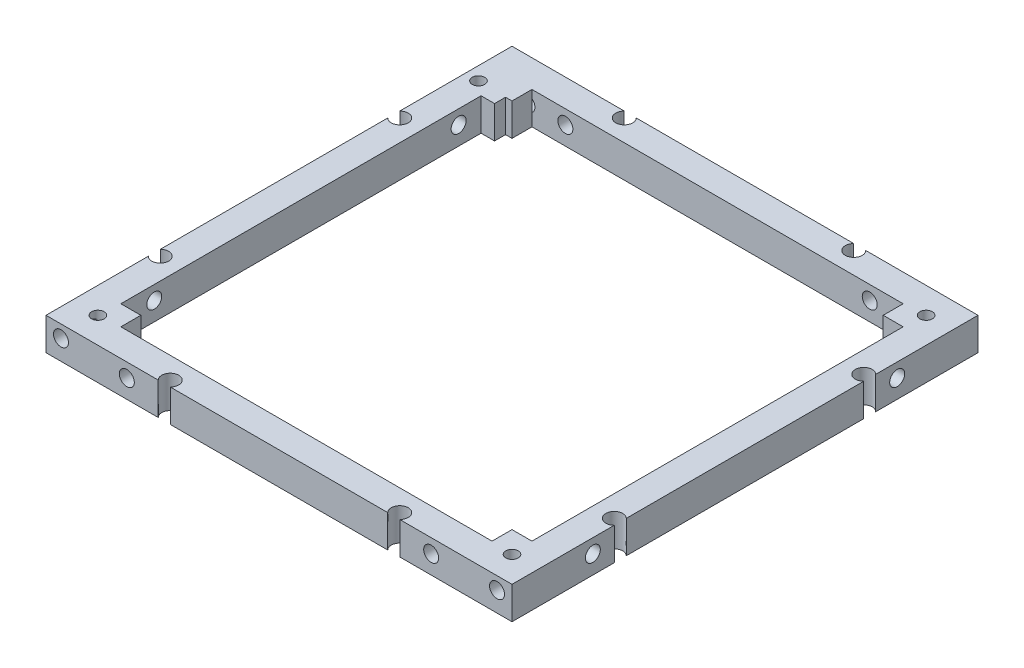
SolidWorks part; units mm, degrees
material "Aluminum"
ref_plane "Front Plane" through (0, 0, 0) normal (0, 0, 1) x (1, 0, 0)
ref_plane "Top Plane" through (0, 0, 0) normal (0, 1, 0) x (1, 0, 0)
ref_plane "Right Plane" through (0, 0, 0) normal (1, 0, 0) x (0, 0, -1)
sketch "Sketch1" plane through (0, 0, 0) normal (0, 1, 0) x (1, 0, 0)
  line L1 (46.7, -46.7) -> (-46.7, -46.7)
  line L2 (46.7, -46.7) -> (46.7, 46.7)
  line L3 (46.7, 46.7) -> (-46.7, 46.7)
  line L4 (-46.7, -46.7) -> (-46.7, 46.7)
  line L5 (46.7, -46.7) -> (-46.7, 46.7) construction
  line L6 (46.7, 46.7) -> (-46.7, -46.7) construction
  line L7 (38.7, -38.7) -> (-38.7, -38.7)
  line L8 (38.7, -38.7) -> (38.7, 38.7)
  line L9 (38.7, 38.7) -> (-38.7, 38.7)
  line L10 (-38.7, -38.7) -> (-38.7, 38.7)
  line L11 (38.7, -38.7) -> (-38.7, 38.7) construction
  line L12 (38.7, 38.7) -> (-38.7, -38.7) construction
  point P0 (0, 0)
  point P6 (0, 0)
  dimension "D1" = 93.4
  dimension "D2" = 93.4
  dimension "D3" = 8
extrude "Boss-Extrude1" add sketch "Sketch1" along normal blind 8
hole_wizard "Ø3.0 (3) Diameter Hole6" positions "Sketch8" profile "Sketch7" hole size "Ø3.0" standard "ANSI Metric"
sketch "Sketch8" plane through (0, 0, 46.7) normal (0, 0, 1) x (1, 0, 0)
  line L0 (46.7, 8) -> (46.7, 0) construction
  line L1 (-46.7, 8) -> (-46.7, 0) construction
  line L2 (-46.7, 0) -> (46.7, 0) construction
  point P0 (43.7, 4)
  point P2 (-43.7, 4)
  dimension "D1" = 3
  dimension "D2" = 3
  dimension "D3" = 4
  dimension "D4" = 4
sketch "Sketch7" plane through (43.7, 4, 46.7) normal (1, 0, 0) x (0, -1, 0)
  line L0 (0, 0) -> (0, 7.5)
  line L1 (0, 7.5) -> (1.5, 7.5)
  line L2 (1.5, 7.5) -> (1.5, 0)
  line L5 (1.5, 0) -> (0, 0)
  line L10 (0, 7.5) -> (-1.5, 7.5) construction
  line L11 (0, -6.35) -> (0, 107.95) construction
  dimension "Hole Dia." = 3
  dimension "Hole Depth" = 7.5
  dimension "Drill Angle" = 180
hole_wizard "Ø3.0 (3) Diameter Hole3" positions "Sketch10" profile "Sketch9" hole size "Ø3.0" standard "ANSI Metric"
sketch "Sketch10" plane through (0, 0, -46.7) normal (0, 0, -1) x (-1, 0, 0)
  line L0 (-46.7, 8) -> (-46.7, 0) construction
  line L1 (46.7, 8) -> (46.7, 0) construction
  line L2 (-46.7, 0) -> (46.7, 0) construction
  point P0 (-43.7, 4)
  point P2 (43.7, 4)
  dimension "D1" = 3
  dimension "D2" = 3
  dimension "D3" = 4
  dimension "D4" = 4
sketch "Sketch9" plane through (43.7, 4, -46.7) normal (1, 0, 0) x (0, 1, 0)
  line L0 (0, 0) -> (0, 7.5)
  line L1 (0, 7.5) -> (1.5, 7.5)
  line L2 (1.5, 7.5) -> (1.5, 0)
  line L5 (1.5, 0) -> (0, 0)
  line L10 (0, 7.5) -> (-1.5, 7.5) construction
  line L11 (0, -6.35) -> (0, 107.95) construction
  dimension "Hole Dia." = 3
  dimension "Hole Depth" = 7.5
  dimension "Drill Angle" = 180
sketch "Sketch27" plane through (0, 8, 0) normal (0, 1, 0) x (1, 0, 0)
  line L0 (-38.7, 38.7) -> (-38.7, -38.7) construction
  line L1 (39.7, -39.7) -> (-39.7, -39.7)
  line L2 (39.7, -39.7) -> (39.7, 39.7)
  line L3 (39.7, 39.7) -> (-39.7, 39.7)
  line L4 (-39.7, -39.7) -> (-39.7, 39.7)
  line L5 (39.7, -39.7) -> (-39.7, 39.7) construction
  line L6 (39.7, 39.7) -> (-39.7, -39.7) construction
  line L7 (38.7, 38.7) -> (-38.7, 38.7) construction
  point P0 (0, 0)
  dimension "D1" = 1
  dimension "D2" = 1
extrude "Cut-Extrude2" cut sketch "Sketch27" against normal blind 10
hole_wizard "Ø3.4 (3.4) Diameter Hole1" positions "Sketch37" profile "Sketch36" hole size "Ø3.4" standard "ANSI Metric" end condition through all
sketch "Sketch37" plane through (0, 0, 0) normal (0, -1, 0) x (-1, 0, 0)
  point P0 (-23, 45.5)
  point P2 (23, 45.5)
  point P4 (45.5, 23)
  point P6 (45.5, -25)
  point P8 (23, -45.5)
  point P10 (-23, -45.5)
  point P12 (-45.5, -25)
  point P14 (-45.5, 25)
sketch "Sketch36" plane through (23, 0, -45.5) normal (1, 0, 0) x (0, 0, -1)
  line L0 (0, 0) -> (0, 8)
  line L1 (0, 8) -> (1.7, 8)
  line L2 (1.7, 8) -> (1.7, 0)
  line L5 (1.7, 0) -> (0, 0)
  line L11 (0, -6.35) -> (0, 107.95) construction
  dimension "Thru Hole Dia." = 3.4
  dimension "Thru Hole Depth" = 8
sketch "Sketch38" plane through (0, 8, 0) normal (0, 1, 0) x (1, 0, 0)
  line L0 (46.7, 46.7) -> (24.2042, 46.7) construction
  line L1 (41.2, -41.2) -> (-41.2, -41.2)
  line L2 (41.2, -41.2) -> (41.2, 41.2)
  line L3 (41.2, 41.2) -> (-41.2, 41.2)
  line L4 (-41.2, -41.2) -> (-41.2, 41.2)
  line L5 (41.2, -41.2) -> (-41.2, 41.2) construction
  line L6 (41.2, 41.2) -> (-41.2, -41.2) construction
  line L7 (-46.7, 46.7) -> (-46.7, 24.2042) construction
  point P0 (0, 0)
  dimension "D1" = 5.5
  dimension "D2" = 5.5
extrude "Cut-Extrude4" cut sketch "Sketch38" against normal blind 10
sketch "Sketch44" plane through (0, 0, 0) normal (0, -1, 0) x (1, 0, 0)
  line L0 (41.2, -41.2) -> (-41.2, -41.2) construction
  line L1 (41.2, -41.2) -> (37.2, -41.2)
  line L2 (41.2, -41.2) -> (41.2, -37.2)
  line L3 (41.2, -37.2) -> (37.2, -37.2)
  line L4 (37.2, -41.2) -> (37.2, -37.2)
  line L5 (41.2, 41.2) -> (41.2, -41.2) construction
  line L6 (0, 0) -> (0, -67.1068) construction
  line L7 (0, 0) -> (66.4168, 0) construction
  line L8 (-37.2, -41.2) -> (-37.2, -37.2)
  line L9 (-41.2, -37.2) -> (-37.2, -37.2)
  line L10 (-41.2, -41.2) -> (-41.2, -37.2)
  line L11 (-41.2, -41.2) -> (-37.2, -41.2)
  line L12 (-41.2, 41.2) -> (-37.2, 41.2)
  line L13 (-41.2, 41.2) -> (-41.2, 37.2)
  line L14 (-41.2, 37.2) -> (-37.2, 37.2)
  line L15 (-37.2, 41.2) -> (-37.2, 37.2)
  line L16 (37.2, 41.2) -> (37.2, 37.2)
  line L17 (41.2, 37.2) -> (37.2, 37.2)
  line L18 (41.2, 41.2) -> (41.2, 37.2)
  line L19 (41.2, 41.2) -> (37.2, 41.2)
  dimension "D1" = 4
  dimension "D2" = 4
extrude "Boss-Extrude2" add sketch "Sketch44" against normal blind 8
sketch "Sketch45" plane through (0, 8, 0) normal (0, 1, 0) x (1, 0, 0)
  line L1 (-42.5, 38.5) -> (-38.5, 38.5)
  line L2 (-42.5, 38.5) -> (-42.5, 35)
  line L3 (-42.5, 35) -> (-38.5, 35)
  line L4 (-38.5, 38.5) -> (-38.5, 35)
  dimension "D1" = 4
  dimension "D2" = 3.5
extrude "Boss-Extrude3" add sketch "Sketch45" against normal blind 8
hole_wizard "Tap Drill for M3x0.5 Tap1" positions "Sketch48" profile "Sketch46" hole size "M3x0.5" standard "ANSI Metric" end condition through all
sketch "Sketch48" plane through (0, 8, 0) normal (0, 1, 0) x (1, 0, 0)
  point P0 (41.5, 41.5)
  point P2 (41.5, -41.5)
  point P4 (-41.5, -41.5)
  point P6 (-44.05, 37.33)
sketch "Sketch46" plane through (41.5, 8, -41.5) normal (1, 0, 0) x (0, 0, 1)
  line L0 (0, 0) -> (0, 8)
  line L1 (0, 8) -> (1.25, 8)
  line L2 (1.25, 8) -> (1.25, 0)
  line L5 (1.25, 0) -> (0, 0)
  line L11 (0, -6.35) -> (0, 107.95) construction
  dimension "Thru Hole Dia." = 2.5
  dimension "Thru Hole Depth" = 8
sketch "Sketch49" plane through (46.7, 0, 0) normal (1, 0, 0) x (0, 0, -1)
  line L0 (46.7, 8) -> (46.7, 0) construction
  line L1 (-46.7, 8) -> (46.7, 8)
  line L2 (-46.7, 8) -> (-46.7, 6.5)
  line L3 (-46.7, 6.5) -> (46.7, 6.5)
  line L4 (46.7, 8) -> (46.7, 6.5)
  dimension "D1" = 1.5
extrude "Cut-Extrude5" cut sketch "Sketch49" against normal blind 146
hole_wizard "Tap Drill for M3x0.5 Tap2" positions "Sketch51" profile "Sketch50" hole size "M3x0.5" standard "ANSI Metric" end condition up to next
sketch "Sketch51" plane through (-46.7, 0, 0) normal (-1, 0, 0) x (0, 0, 1)
  point P0 (30.5, 3.7)
  point P3 (-30.5, 3.7)
sketch "Sketch50" plane through (-46.7, 3.7, 30.5) normal (0, 1, 0) x (0, 0, 1)
  line L0 (0, 0) -> (0, 5.5)
  line L1 (0, 5.5) -> (1.5, 5.5)
  line L2 (1.5, 5.5) -> (1.5, 0)
  line L5 (1.5, 0) -> (0, 0)
  line L11 (0, -6.35) -> (0, 107.95) construction
  dimension "Thru Hole Dia." = 3
  dimension "Thru Hole Depth" = 5.5
hole_wizard "Tap Drill for M3x0.5 Tap3" positions "Sketch53" profile "Sketch52" hole size "M3x0.5" standard "ANSI Metric" end condition up to next
sketch "Sketch53" plane through (0, 0, -46.7) normal (0, 0, -1) x (-1, 0, 0)
  point P0 (30.5, 3.7)
  point P3 (-30.5, 3.7)
sketch "Sketch52" plane through (-30.5, 3.7, -46.7) normal (1, 0, 0) x (0, 1, 0)
  line L0 (0, 0) -> (0, 5.5)
  line L1 (0, 5.5) -> (1.5, 5.5)
  line L2 (1.5, 5.5) -> (1.5, 0)
  line L5 (1.5, 0) -> (0, 0)
  line L11 (0, -6.35) -> (0, 107.95) construction
  dimension "Thru Hole Dia." = 3
  dimension "Thru Hole Depth" = 5.5
hole_wizard "Tap Drill for M3x0.5 Tap4" positions "Sketch55" profile "Sketch54" hole size "M3x0.5" standard "ANSI Metric" end condition up to next
sketch "Sketch55" plane through (46.7, 0, 0) normal (1, 0, 0) x (0, 0, -1)
  point P0 (30.5, 3.7)
  point P3 (-30.5, 3.7)
sketch "Sketch54" plane through (46.7, 3.7, -30.5) normal (0, 1, 0) x (0, 0, -1)
  line L0 (0, 0) -> (0, 5.5)
  line L1 (0, 5.5) -> (1.5, 5.5)
  line L2 (1.5, 5.5) -> (1.5, 0)
  line L5 (1.5, 0) -> (0, 0)
  line L11 (0, -6.35) -> (0, 107.95) construction
  dimension "Thru Hole Dia." = 3
  dimension "Thru Hole Depth" = 5.5
hole_wizard "Tap Drill for M3x0.5 Tap5" positions "Sketch57" profile "Sketch56" hole size "M3x0.5" standard "ANSI Metric" end condition up to next
sketch "Sketch57" plane through (0, 0, 46.7) normal (0, 0, 1) x (1, 0, 0)
  point P0 (30.5, 3.7)
  point P3 (-30.5, 3.7)
sketch "Sketch56" plane through (30.5, 3.7, 46.7) normal (1, 0, 0) x (0, -1, 0)
  line L0 (0, 0) -> (0, 5.5)
  line L1 (0, 5.5) -> (1.5, 5.5)
  line L2 (1.5, 5.5) -> (1.5, 0)
  line L5 (1.5, 0) -> (0, 0)
  line L11 (0, -6.35) -> (0, 107.95) construction
  dimension "Thru Hole Dia." = 3
  dimension "Thru Hole Depth" = 5.5
hole_wizard "Tap Drill for M3x0.5 Tap6" positions "Sketch59" profile "Sketch58" hole size "M3x0.5" standard "ANSI Metric"
sketch "Sketch59" plane through (0, 0, -46.7) normal (0, 0, -1) x (-1, 0, 0)
  line L0 (0, 0) -> (0, -19.6512) construction
  point P0 (38.1, 3.7)
  point P2 (-38.1, 3.7)
  dimension "D1" = 38.1
  dimension "D2" = 38.1
sketch "Sketch58" plane through (-38.1, 3.7, -46.7) normal (1, 0, 0) x (0, 1, 0)
  line L0 (0, 0) -> (0, 5.5)
  line L1 (0, 5.5) -> (1.5, 5.5)
  line L2 (1.5, 5.5) -> (1.5, 0)
  line L5 (1.5, 0) -> (0, 0)
  line L10 (0, 5.5) -> (-1.5, 5.5) construction
  line L11 (0, -6.35) -> (0, 107.95) construction
  dimension "Hole Dia." = 3
  dimension "Hole Depth" = 5.5
  dimension "Drill Angle" = 180
